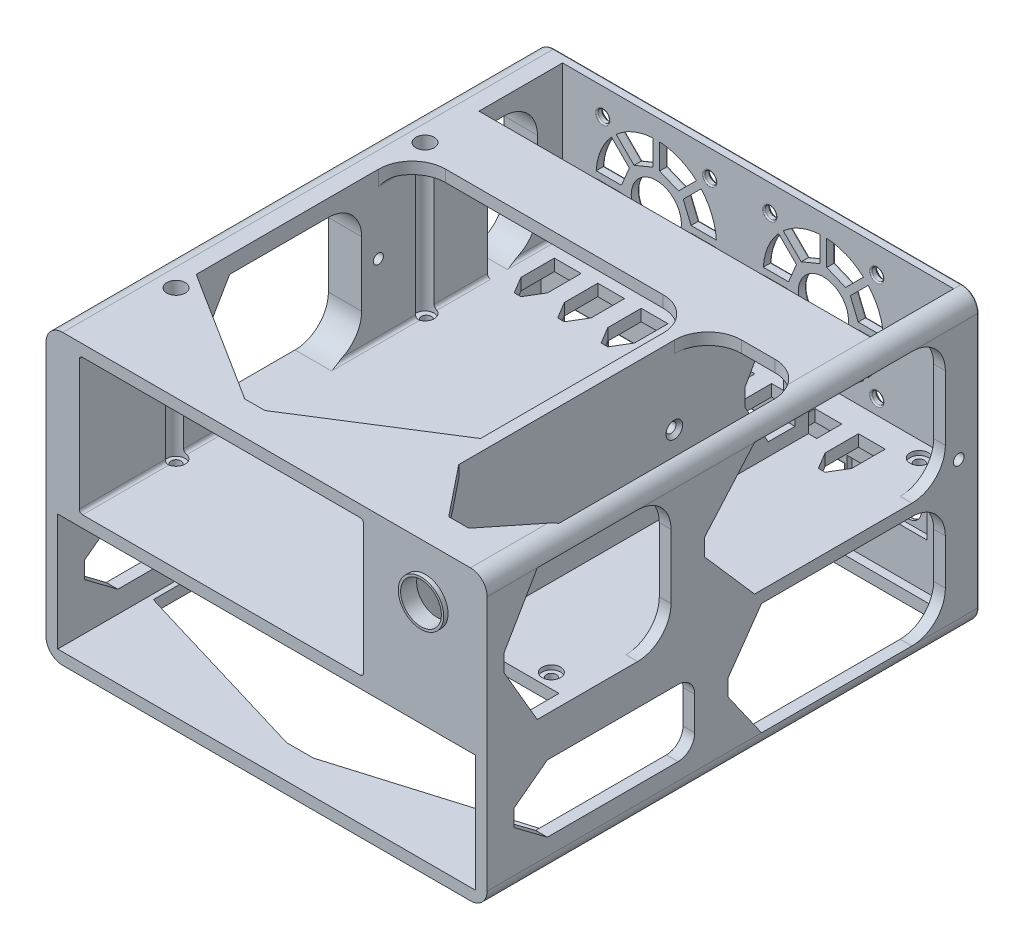
SolidWorks part; units mm, degrees
note: The reader was unsure of these and kept them because the rebuilt part matched: shared geometry of "草图12<5>", "草图14<3>", "草图12<6>", "草图12<7>".
ref_plane "Front Plane" through (0, 0, 0) normal (0, 0, 1) x (1, 0, 0)
ref_plane "Top Plane" through (0, 0, 0) normal (0, 1, 0) x (1, 0, 0)
ref_plane "Right Plane" through (0, 0, 0) normal (1, 0, 0) x (0, 0, -1)
other "Configuration Table"
sketch "草图1" plane through (0, 0, 0) normal (0, 0, 1) x (1, 0, 0)
  line L1 (-60.7557, 55.9139) -> (61.2443, 55.9139)
  line L2 (-65.7557, 50.9139) -> (-65.7557, -25.3861)
  line L3 (-60.7557, -30.3861) -> (61.2443, -30.3861)
  line L4 (66.2443, 50.9139) -> (66.2443, -25.3861)
  arc A0 (-65.7557, -25.3861) -> (-60.7557, -30.3861) centre (-60.7557, -25.3861) ccw
  arc A1 (61.2443, -30.3861) -> (66.2443, -25.3861) centre (61.2443, -25.3861) ccw
  arc A2 (66.2443, 50.9139) -> (61.2443, 55.9139) centre (61.2443, 50.9139) ccw
  arc A3 (-65.7557, 50.9139) -> (-60.7557, 55.9139) centre (-60.7557, 50.9139) cw
  point P8 (66.2443, -30.3861)
  point P11 (66.2443, 55.9139)
  point P14 (-65.7557, 55.9139)
  dimension "D3" = 5
  dimension "D1" = 132
  dimension "D2" = 86.3
extrude "凸台-拉伸1" add sketch "草图1" along normal blind 147.1
sketch "草图2" plane through (0, 0, 147.1) normal (0, 0, 1) x (1, 0, 0)
  line L0 (-65.7557, 50.9139) -> (-65.7557, -25.3861) construction
  line L1 (-54.8057, 52.4139) -> (28.2443, 52.4139)
  line L2 (-55.8057, 51.4139) -> (-55.8057, 12.6139)
  line L3 (-54.8057, 11.6139) -> (28.2443, 11.6139)
  line L4 (29.2443, 51.4139) -> (29.2443, 12.6139)
  line L5 (32.7443, 52.4139) -> (62.7443, 52.4139)
  line L6 (32.7443, 52.4139) -> (32.7443, 11.6139)
  line L7 (32.7443, 11.6139) -> (62.7443, 11.6139)
  line L8 (62.7443, 52.4139) -> (62.7443, 11.6139)
  line L9 (-62.2557, 8.1139) -> (62.7443, 8.1139)
  line L10 (-62.2557, 8.1139) -> (-62.2557, -26.8861)
  line L11 (-62.2557, -26.8861) -> (62.7443, -26.8861)
  line L12 (62.7443, 8.1139) -> (62.7443, -26.8861)
  line L13 (61.2443, 55.9139) -> (-60.7557, 55.9139) construction
  line L14 (-60.7557, -30.3861) -> (61.2443, -30.3861) construction
  line L15 (66.2443, -25.3861) -> (66.2443, 50.9139) construction
  arc A0 (-55.8057, 12.6139) -> (-54.8057, 11.6139) centre (-54.8057, 12.6139) ccw
  arc A1 (28.2443, 11.6139) -> (29.2443, 12.6139) centre (28.2443, 12.6139) ccw
  arc A2 (29.2443, 51.4139) -> (28.2443, 52.4139) centre (28.2443, 51.4139) ccw
  arc A3 (-55.8057, 51.4139) -> (-54.8057, 52.4139) centre (-54.8057, 51.4139) cw
  point P24 (29.2443, 11.6139)
  point P27 (29.2443, 52.4139)
  point P30 (-55.8057, 52.4139)
  dimension "D13" = 1
  dimension "D1" = 9.95
  dimension "D2" = 3.5
  dimension "D3" = 40.8
  dimension "D4" = 3.5
  dimension "D5" = 85.05
  dimension "D6" = 3.5
  dimension "D7" = 3.5
  dimension "D8" = 3.5
  dimension "D9" = 3.5
  dimension "D10" = 3.5
  dimension "D11" = 3.5
  dimension "D12" = 3.5
extrude "切除-拉伸1" cut sketch "草图2" against normal blind 144.6
sketch "草图4" plane through (0, 0, 0) normal (0, 0, -1) x (-1, 0, 0)
  line L0 (65.7557, 50.9139) -> (65.7557, -25.3861) construction
  line L1 (7.7557, 52.0139) -> (47.7557, 52.0139)
  line L2 (7.7557, 52.0139) -> (7.7557, 12.0139)
  line L3 (7.7557, 12.0139) -> (47.7557, 12.0139)
  line L4 (47.7557, 52.0139) -> (47.7557, 12.0139)
  line L5 (-42.2443, 52.0139) -> (-2.2443, 52.0139)
  line L6 (-42.2443, 52.0139) -> (-42.2443, 12.0139)
  line L7 (-42.2443, 12.0139) -> (-2.2443, 12.0139)
  line L8 (-2.2443, 52.0139) -> (-2.2443, 12.0139)
  line L9 (-61.2443, 55.9139) -> (60.7557, 55.9139) construction
  line L10 (-8.829, 44.0151) -> (-14.1764, 38.6676)
  line L11 (-11.8346, 33.0139) -> (-14.1764, 38.6676)
  line L12 (-15.5907, 40.0818) -> (-21.2443, 42.4236)
  line L13 (-23.2443, 42.4236) -> (-28.898, 40.0818)
  line L14 (-30.3122, 38.6676) -> (-32.654, 33.0139)
  line L15 (-32.654, 31.0139) -> (-30.3122, 25.3603)
  line L16 (-28.898, 23.946) -> (-23.2443, 21.6042)
  line L17 (-21.2443, 21.6042) -> (-15.5907, 23.946)
  line L18 (-14.1764, 25.3603) -> (-11.8346, 31.0139)
  line L20 (-23.2443, 49.9861) -> (-23.2443, 42.4236)
  line L22 (-21.2443, 49.9861) -> (-21.2443, 42.4236)
  line L23 (-10.2432, 45.4293) -> (-15.5907, 40.0818)
  line L24 (-4.2721, 31.0139) -> (-11.8346, 31.0139)
  line L25 (-4.2721, 33.0139) -> (-11.8346, 33.0139)
  line L26 (-10.2432, 18.5986) -> (-15.5907, 23.946)
  line L27 (-8.829, 20.0128) -> (-14.1764, 25.3603)
  line L28 (-23.2443, 14.0417) -> (-23.2443, 21.6042)
  line L29 (-21.2443, 14.0417) -> (-21.2443, 21.6042)
  line L30 (-35.6597, 20.0128) -> (-30.3122, 25.3603)
  line L31 (-34.2455, 18.5986) -> (-28.898, 23.946)
  line L32 (-40.2165, 33.0139) -> (-32.654, 33.0139)
  line L33 (-40.2165, 31.0139) -> (-32.654, 31.0139)
  line L34 (-34.2455, 45.4293) -> (-28.898, 40.0818)
  line L35 (-35.6597, 44.0151) -> (-30.3122, 38.6676)
  line L36 (28.7557, 49.9861) -> (28.7557, 42.4236)
  line L37 (28.7557, 42.4236) -> (34.4093, 40.0818)
  line L38 (2.7557, 52.0139) -> (2.7557, 12.0139) construction
  line L39 (39.7568, 45.4293) -> (34.4093, 40.0818)
  line L40 (41.171, 44.0151) -> (35.8236, 38.6676)
  line L41 (35.8236, 38.6676) -> (38.1654, 33.0139)
  line L42 (45.7279, 33.0139) -> (38.1654, 33.0139)
  line L43 (45.7279, 31.0139) -> (38.1654, 31.0139)
  line L44 (38.1654, 31.0139) -> (35.8236, 25.3603)
  line L45 (41.171, 20.0128) -> (35.8236, 25.3603)
  line L46 (39.7568, 18.5986) -> (34.4093, 23.946)
  line L47 (34.4093, 23.946) -> (28.7557, 21.6042)
  line L48 (28.7557, 14.0417) -> (28.7557, 21.6042)
  line L49 (26.7557, 14.0417) -> (26.7557, 21.6042)
  line L50 (26.7557, 21.6042) -> (21.102, 23.946)
  line L51 (15.7545, 18.5986) -> (21.102, 23.946)
  line L52 (14.3403, 20.0128) -> (19.6878, 25.3603)
  line L53 (19.6878, 25.3603) -> (17.346, 31.0139)
  line L54 (9.7835, 31.0139) -> (17.346, 31.0139)
  line L55 (9.7835, 33.0139) -> (17.346, 33.0139)
  line L56 (17.346, 33.0139) -> (19.6878, 38.6676)
  line L57 (14.3403, 44.0151) -> (19.6878, 38.6676)
  line L58 (15.7545, 45.4293) -> (21.102, 40.0818)
  line L59 (21.102, 40.0818) -> (26.7557, 42.4236)
  line L60 (26.7557, 49.9861) -> (26.7557, 42.4236)
  circle A0 centre (-38.2443, 48.0139) radius 1.75
  circle A1 centre (-6.2443, 48.0139) radius 1.75
  circle A2 centre (-38.2443, 16.0139) radius 1.75
  circle A3 centre (-6.2443, 16.0139) radius 1.75
  circle A4 centre (-22.2443, 32.0139) radius 7.5
  circle A5 centre (43.7557, 16.0139) radius 1.75
  arc A6 (-23.2443, 49.9861) -> (-34.2455, 45.4293) centre (-22.2443, 32.0139) ccw
  arc A7 (-10.2432, 45.4293) -> (-21.2443, 49.9861) centre (-22.2443, 32.0139) ccw
  arc A8 (-4.2721, 33.0139) -> (-8.829, 44.0151) centre (-22.2443, 32.0139) ccw
  arc A9 (-8.829, 20.0128) -> (-4.2721, 31.0139) centre (-22.2443, 32.0139) ccw
  circle A10 centre (11.7557, 16.0139) radius 1.75
  arc A11 (-21.2443, 14.0417) -> (-10.2432, 18.5986) centre (-22.2443, 32.0139) ccw
  arc A12 (-34.2455, 18.5986) -> (-23.2443, 14.0417) centre (-22.2443, 32.0139) ccw
  arc A13 (-40.2165, 31.0139) -> (-35.6597, 20.0128) centre (-22.2443, 32.0139) ccw
  arc A14 (-35.6597, 44.0151) -> (-40.2165, 33.0139) centre (-22.2443, 32.0139) ccw
  circle A15 centre (11.7557, 48.0139) radius 1.75
  circle A16 centre (43.7557, 48.0139) radius 1.75
  circle A17 centre (27.7557, 32.0139) radius 7.5
  arc A18 (41.171, 44.0151) -> (45.7279, 33.0139) centre (27.7557, 32.0139) cw
  arc A19 (28.7557, 49.9861) -> (39.7568, 45.4293) centre (27.7557, 32.0139) cw
  arc A20 (45.7279, 31.0139) -> (41.171, 20.0128) centre (27.7557, 32.0139) cw
  arc A21 (39.7568, 18.5986) -> (28.7557, 14.0417) centre (27.7557, 32.0139) cw
  arc A22 (26.7557, 14.0417) -> (15.7545, 18.5986) centre (27.7557, 32.0139) cw
  arc A23 (14.3403, 20.0128) -> (9.7835, 31.0139) centre (27.7557, 32.0139) cw
  arc A24 (9.7835, 33.0139) -> (14.3403, 44.0151) centre (27.7557, 32.0139) cw
  arc A25 (15.7545, 45.4293) -> (26.7557, 49.9861) centre (27.7557, 32.0139) cw
  point P68 (-22.2443, 32.0139)
  dimension "D9" = 3.5
  dimension "D10" = 20
  dimension "D11" = 20
  dimension "D13" = 36
  dimension "D14" = 15
  dimension "D15" = 16
  dimension "D16" = 16
  dimension "D17" = 16
  dimension "D18" = 16
  dimension "D19" = 16
  dimension "D20" = 16
  dimension "D21" = 16
  dimension "D22" = 16
  dimension "D1" = 40
  dimension "D2" = 10
  dimension "D3" = 40
  dimension "D4" = 18
  dimension "D5" = 40
  dimension "D6" = 40
  dimension "D7" = 3.9
  dimension "D8" = 3.9
  dimension "D23" = 2
  dimension "D24" = 1
  dimension "D25" = 8
extrude "切除-拉伸2" cut sketch "草图4" against normal blind 2.5 contours L20 A6 L34 L13 | L23 A7 L22 L12 | A1 | L25 A8 L10 L11 | L27 A9 L24 L18 | L29 A11 L26 L17 | L31 A12 L28 L16 | L33 A13 L30 L15 | L35 A14 L32 L14 | A4 | A22 L49 L50 L51 | A20 L43 L44 L45 | A18 L40 L41 L42 | A21 L46 L47 L48 | A23 L52 L53 L54 | A24 L55 L56 L57 | A25 L58 L59 L60 | A19 L36 L37 L39 | A17 | A16 | A5 | A0 | A3 | A2 | A10 | A15
sketch "草图5" plane through (0, 0, 0) normal (0, 0, -1) x (-1, 0, 0)
  line L0 (-61.2443, 55.9139) -> (60.7557, 55.9139) construction
  line L1 (-28.3443, -5.8861) -> (-11.1443, -5.8861)
  line L2 (-28.3443, -5.8861) -> (-28.3443, -20.3861)
  line L3 (-28.3443, -20.3861) -> (-11.1443, -20.3861)
  line L4 (-11.1443, -5.8861) -> (-11.1443, -20.3861)
  line L5 (-8.2443, -5.6861) -> (7.2557, -5.6861)
  line L6 (-8.2443, -5.6861) -> (-8.2443, -13.6861)
  line L7 (-8.2443, -13.6861) -> (7.2557, -13.6861)
  line L8 (7.2557, -5.6861) -> (7.2557, -13.6861)
  line L9 (9.9557, -6.2861) -> (26.2557, -6.2861)
  line L10 (9.9557, -6.2861) -> (9.9557, -22.8861)
  line L11 (9.9557, -22.8861) -> (26.2557, -22.8861)
  line L12 (26.2557, -6.2861) -> (26.2557, -22.8861)
  line L13 (28.3557, -6.3861) -> (44.3557, -6.3861)
  line L14 (28.3557, -6.3861) -> (28.3557, -12.8861)
  line L15 (28.3557, -12.8861) -> (44.3557, -12.8861)
  line L16 (44.3557, -6.3861) -> (44.3557, -12.8861)
  line L17 (47.4557, -6.4861) -> (57.4557, -6.4861)
  line L18 (47.4557, -6.4861) -> (47.4557, -19.4861)
  line L19 (47.4557, -19.4861) -> (57.4557, -19.4861)
  line L20 (57.4557, -6.4861) -> (57.4557, -19.4861)
  line L21 (65.7557, 50.9139) -> (65.7557, -25.3861) construction
  circle A0 centre (-46.2943, -8.1861) radius 3.75
  circle A1 centre (-35.1443, -8.1861) radius 3.75
  point P28 (28.3557, -9.6361)
  dimension "D21" = 7.5
  dimension "D22" = 6.8
  dimension "D23" = 2.3
  dimension "D24" = 11.15
  dimension "D25" = 2.3
  dimension "D1" = 62.4
  dimension "D2" = 8.3
  dimension "D3" = 13
  dimension "D4" = 10
  dimension "D5" = 62.3
  dimension "D6" = 3.1
  dimension "D7" = 16
  dimension "D8" = 6.5
  dimension "D9" = 62.2
  dimension "D10" = 61.6
  dimension "D11" = 61.8
  dimension "D12" = 2.1
  dimension "D13" = 16.3
  dimension "D14" = 16.6
  dimension "D15" = 2.7
  dimension "D16" = 15.5
  dimension "D17" = 8
  dimension "D18" = 2.9
  dimension "D19" = 17.2
  dimension "D20" = 14.5
extrude "切除-拉伸3" cut sketch "草图5" against normal blind 2.5
sketch "草图6" plane through (0, 0, 2.5) normal (0, 0, 1) x (1, 0, 0)
  line L1 (29.2943, -3.1861) -> (53.2943, -3.1861)
  line L2 (29.2943, -3.1861) -> (29.2943, -13.1861)
  line L3 (29.2943, -13.1861) -> (53.2943, -13.1861)
  line L4 (53.2943, -3.1861) -> (53.2943, -13.1861)
  circle A0 centre (46.2943, -8.1861) radius 3.75 construction
  dimension "D2" = 5
  dimension "D1" = 7
  dimension "D3" = 10
  dimension "D4" = 24
extrude "切除-拉伸4" cut sketch "草图6" against normal blind 1.5
sketch "草图7" plane through (0, 11.6139, 0) normal (0, 1, 0) x (1, 0, 0)
  line L0 (61.2443, 0) -> (-60.7557, 0) construction
  line L1 (66.2443, -147.1) -> (66.2443, 0) construction
  line L2 (-65.7557, -147.1) -> (-65.7557, 0) construction
  line L3 (-50.7557, -10) -> (-42.7557, -10)
  line L4 (-42.7557, -10) -> (-42.7557, -20)
  line L5 (-42.7557, -20) -> (-45.7557, -25)
  line L6 (-45.7557, -25) -> (-47.7557, -25)
  line L7 (-47.7557, -25) -> (-50.7557, -20)
  line L8 (-50.7557, -20) -> (-50.7557, -10)
  line L9 (-37.7557, -10) -> (-29.7557, -10)
  line L10 (-29.7557, -10) -> (-29.7557, -20)
  line L11 (-29.7557, -20) -> (-32.7557, -25)
  line L12 (-32.7557, -25) -> (-34.7557, -25)
  line L13 (-34.7557, -25) -> (-37.7557, -20)
  line L14 (-37.7557, -20) -> (-37.7557, -10)
  line L15 (-24.7557, -10) -> (-16.7557, -10)
  line L16 (-16.7557, -10) -> (-16.7557, -20)
  line L17 (-16.7557, -20) -> (-19.7557, -25)
  line L18 (-19.7557, -25) -> (-21.7557, -25)
  line L19 (-21.7557, -25) -> (-24.7557, -20)
  line L20 (-24.7557, -20) -> (-24.7557, -10)
  line L21 (-11.7557, -10) -> (-3.7557, -10)
  line L22 (-3.7557, -10) -> (-3.7557, -20)
  line L23 (-3.7557, -20) -> (-6.7557, -25)
  line L24 (-6.7557, -25) -> (-8.7557, -25)
  line L25 (-8.7557, -25) -> (-11.7557, -20)
  line L26 (-11.7557, -20) -> (-11.7557, -10)
  line L27 (1.2443, -10) -> (9.2443, -10)
  line L28 (9.2443, -10) -> (9.2443, -20)
  line L29 (9.2443, -20) -> (6.2443, -25)
  line L30 (6.2443, -25) -> (4.2443, -25)
  line L31 (4.2443, -25) -> (1.2443, -20)
  line L32 (1.2443, -20) -> (1.2443, -10)
  line L33 (14.2443, -10) -> (22.2443, -10)
  line L34 (22.2443, -10) -> (22.2443, -20)
  line L35 (22.2443, -20) -> (19.2443, -25)
  line L36 (19.2443, -25) -> (17.2443, -25)
  line L37 (17.2443, -25) -> (14.2443, -20)
  line L38 (14.2443, -20) -> (14.2443, -10)
  line L39 (27.2443, -10) -> (35.2443, -10)
  line L40 (35.2443, -10) -> (35.2443, -20)
  line L41 (35.2443, -20) -> (32.2443, -25)
  line L42 (32.2443, -25) -> (30.2443, -25)
  line L43 (30.2443, -25) -> (27.2443, -20)
  line L44 (27.2443, -20) -> (27.2443, -10)
  line L45 (40.2443, -10) -> (48.2443, -10)
  line L46 (48.2443, -10) -> (48.2443, -20)
  line L47 (48.2443, -20) -> (45.2443, -25)
  line L48 (45.2443, -25) -> (43.2443, -25)
  line L49 (43.2443, -25) -> (40.2443, -20)
  line L50 (40.2443, -20) -> (40.2443, -10)
  line L51 (61.2443, -147.1) -> (-60.7557, -147.1) construction
  line L52 (32.7443, -122.1) -> (62.7443, -122.1)
  line L53 (32.7443, -122.1) -> (32.7443, -147.1)
  line L54 (32.7443, -147.1) -> (62.7443, -147.1)
  line L55 (62.7443, -122.1) -> (62.7443, -147.1)
  circle A0 centre (-55.3557, -43.7) radius 1.5
  circle A1 centre (55.6443, -7.2) radius 1.5
  circle A2 centre (56.1443, -117.8) radius 1.5
  circle A3 centre (-55.3557, -118.6) radius 1.5
  dimension "D1" = 3
  dimension "D2" = 7.2
  dimension "D3" = 10.6
  dimension "D4" = 10.1
  dimension "D5" = 110.6
  dimension "D6" = 43.7
  dimension "D7" = 10.4
  dimension "D8" = 74.9
  dimension "D9" = 10.4
  dimension "D10" = 10
  dimension "D11" = 15
  dimension "D12" = 8
  dimension "D13" = 2
  dimension "D14" = 3
  dimension "D15" = 5
  dimension "D16" = 5
  dimension "D17" = 15
  dimension "D19" = 5
  dimension "D20" = 3.5
  dimension "D21" = 30
  dimension "D22" = 25
  dimension "D18" = 8
extrude "切除-拉伸5" cut sketch "草图7" against normal blind 3.5
sketch "草图8" plane through (0, 11.6139, 0) normal (0, 1, 0) x (1, 0, 0)
  line L0 (-65.7557, -147.1) -> (-65.7557, 0) construction
  line L1 (61.2443, 0) -> (-60.7557, 0) construction
  circle A0 centre (-55.7557, -43.7) radius 2.75
  circle A1 centre (-55.3557, -118.6) radius 2.75
  circle A2 centre (56.1443, -117.8) radius 2.75
  circle A3 centre (55.6443, -7.2) radius 2.75
  dimension "D1" = 5.5
  dimension "D2" = 10
  dimension "D3" = 43.7
extrude "切除-拉伸6" cut sketch "草图8" against normal blind 1.3 and the other way blind 50
sketch "草图9" plane through (0, 55.9139, 0) normal (0, 1, 0) x (1, 0, 0)
  line L0 (-55.8057, -112.1) -> (-55.8057, -57.5)
  line L1 (-55.8057, -2.5) -> (61.2443, -2.5)
  line L2 (-55.8057, -2.5) -> (-55.8057, -27.5)
  line L3 (-55.8057, -27.5) -> (61.2443, -27.5)
  line L4 (61.2443, -2.5) -> (61.2443, -27.5)
  line L5 (-45.8057, -47.5) -> (19.2443, -47.5)
  line L6 (29.2443, -57.5) -> (29.2443, -112.1)
  line L7 (29.2443, -112.1) -> (-10.2807, -137.1)
  line L8 (-10.2807, -137.1) -> (-16.2807, -137.1)
  line L9 (-16.2807, -137.1) -> (-55.8057, -112.1)
  line L10 (32.7443, -122.1) -> (32.7443, -57.5)
  line L11 (42.7443, -47.5) -> (52.7443, -47.5)
  line L12 (62.7443, -57.5) -> (62.7443, -122.1)
  line L13 (62.7443, -122.1) -> (50.7443, -137.1)
  line L14 (50.7443, -137.1) -> (44.7443, -137.1)
  line L15 (44.7443, -137.1) -> (32.7443, -122.1)
  line L16 (61.2443, 0) -> (-60.7557, 0) construction
  line L17 (66.2443, -147.1) -> (66.2443, 0) construction
  line L18 (-65.7557, -147.1) -> (-65.7557, 0) construction
  line L19 (61.2443, -147.1) -> (-60.7557, -147.1) construction
  arc A0 (-55.8057, -57.5) -> (-45.8057, -47.5) centre (-45.8057, -57.5) cw
  arc A1 (29.2443, -57.5) -> (19.2443, -47.5) centre (19.2443, -57.5) ccw
  arc A2 (62.7443, -57.5) -> (52.7443, -47.5) centre (52.7443, -57.5) ccw
  arc A3 (32.7443, -57.5) -> (42.7443, -47.5) centre (42.7443, -57.5) cw
  point P26 (-55.8057, -47.5)
  point P29 (29.2443, -47.5)
  dimension "D21" = 10
  dimension "D1" = 2.5
  dimension "D2" = 5
  dimension "D3" = 9.95
  dimension "D4" = 25
  dimension "D5" = 20
  dimension "D6" = 10
  dimension "D7" = 9.95
  dimension "D8" = 85.05
  dimension "D9" = 6
  dimension "D10" = 39.525
  dimension "D11" = 25
  dimension "D12" = 25
  dimension "D13" = 20
  dimension "D14" = 10
  dimension "D15" = 3.5
  dimension "D16" = 3.5
  dimension "D17" = 6
  dimension "D18" = 12
  dimension "D19" = 15
  dimension "D20" = 15
extrude "切除-拉伸7" cut sketch "草图9" against normal blind 6
sketch "草图10" plane through (0, 11.6139, 0) normal (0, 1, 0) x (1, 0, 0)
  line L0 (61.2443, -2.5) -> (-55.8057, -2.5) construction
  line L1 (27.2443, -2.5) -> (33.7443, -2.5)
  line L2 (27.2443, -2.5) -> (27.2443, -17.5)
  line L3 (27.2443, -17.5) -> (33.7443, -17.5)
  line L4 (33.7443, -2.5) -> (33.7443, -17.5)
  line L6 (32.7443, -2.5) -> (32.7443, -10) construction
  line L7 (29.2443, -2.5) -> (29.2443, -27.5) construction
  dimension "D1" = 1
  dimension "D2" = 2
  dimension "D3" = 15
extrude "切除-拉伸8" cut sketch "草图10" along normal blind 48
sketch "草图11" plane through (66.2443, 0, 0) normal (1, 0, 0) x (0, 0, -1)
  line L0 (-132.1, 50.9139) -> (-102.1, 50.9139)
  line L1 (-92.1, 40.9139) -> (-92.1, 21.6139)
  line L2 (-102.1, 11.6139) -> (-132.1, 11.6139)
  line L3 (-132.1, 11.6139) -> (-142.1, 28.7639)
  line L4 (-142.1, 28.7639) -> (-142.1, 33.7639)
  line L5 (-142.1, 33.7639) -> (-132.1, 50.9139)
  line L6 (-67.1, 50.9139) -> (-20, 50.9139)
  line L7 (-10, 40.9139) -> (-10, 21.6139)
  line L8 (-20, 11.6139) -> (-67.1, 11.6139)
  line L9 (-67.1, 11.6139) -> (-82.1, 28.7639)
  line L10 (-82.1, 28.7639) -> (-82.1, 33.7639)
  line L11 (-82.1, 33.7639) -> (-67.1, 50.9139)
  line L12 (-65, 8.1139) -> (-20, 8.1139)
  line L13 (-10, -1.8861) -> (-10, -15.3861)
  line L14 (-20, -25.3861) -> (-65, -25.3861)
  line L15 (-65, -25.3861) -> (-75, -11.1361)
  line L16 (-75, -11.1361) -> (-75, -6.1361)
  line L17 (-75, -6.1361) -> (-65, 8.1139)
  line L18 (0, -25.3861) -> (0, 50.9139) construction
  line L19 (-147.1, -25.3861) -> (-147.1, 50.9139) construction
  line L20 (-147.1, 55.9139) -> (-123.975, 55.9139) construction
  line L21 (-129.1, -0.3861) -> (-90, -0.3861)
  line L22 (-147.1, -30.3861) -> (0, -30.3861) construction
  line L23 (-85, -5.3861) -> (-85, -15.3861)
  line L24 (-90, -20.3861) -> (-129.1, -20.3861)
  line L25 (-129.1, -20.3861) -> (-139.1, -12.8861)
  line L26 (-139.1, -12.8861) -> (-139.1, -7.8861)
  line L27 (-139.1, -7.8861) -> (-129.1, -0.3861)
  arc A0 (-102.1, 11.6139) -> (-92.1, 21.6139) centre (-102.1, 21.6139) ccw
  arc A1 (-92.1, 40.9139) -> (-102.1, 50.9139) centre (-102.1, 40.9139) ccw
  arc A2 (-10, 40.9139) -> (-20, 50.9139) centre (-20, 40.9139) ccw
  arc A3 (-20, 11.6139) -> (-10, 21.6139) centre (-20, 21.6139) ccw
  arc A4 (-20, -25.3861) -> (-10, -15.3861) centre (-20, -15.3861) ccw
  arc A5 (-10, -1.8861) -> (-20, 8.1139) centre (-20, -1.8861) ccw
  arc A6 (-90, -20.3861) -> (-85, -15.3861) centre (-90, -15.3861) ccw
  arc A7 (-85, -5.3861) -> (-90, -0.3861) centre (-90, -5.3861) ccw
  point P29 (-92.1, 11.6139)
  point P32 (-92.1, 50.9139)
  point P35 (-10, 50.9139)
  point P38 (-10, 11.6139)
  point P41 (-10, -25.3861)
  point P44 (-10, 8.1139)
  point P53 (-85, -20.3861)
  point P56 (-85, -0.3861)
  dimension "D24" = 10
  dimension "D33" = 5
  dimension "D1" = 10
  dimension "D2" = 10
  dimension "D3" = 65
  dimension "D4" = 5
  dimension "D5" = 5
  dimension "D6" = 39.3
  dimension "D7" = 5
  dimension "D8" = 17.15
  dimension "D9" = 10
  dimension "D10" = 10
  dimension "D11" = 50
  dimension "D12" = 10
  dimension "D13" = 5
  dimension "D14" = 39.3
  dimension "D15" = 17.15
  dimension "D16" = 15
  dimension "D17" = 15
  dimension "D18" = 5
  dimension "D19" = 33.5
  dimension "D20" = 5
  dimension "D21" = 14.25
  dimension "D22" = 10
  dimension "D23" = 10
  dimension "D25" = 10
  dimension "D26" = 5
  dimension "D27" = 8
  dimension "D28" = 10
  dimension "D29" = 20
  dimension "D30" = 7.5
  dimension "D31" = 10
  dimension "D32" = 10
extrude "切除-拉伸9" cut sketch "草图11" against normal blind 3.5
sketch "草图12" plane through (-65.7557, 0, 0) normal (-1, 0, 0) x (0, 0, 1)
  line L0 (42.6, 50.9139) -> (20, 50.9139)
  line L1 (10, 40.9139) -> (10, 21.6139)
  line L2 (20, 11.6139) -> (42.6, 11.6139)
  line L3 (42.6, 11.6139) -> (52.6, 28.7639)
  line L4 (52.6, 28.7639) -> (52.6, 33.7639)
  line L5 (52.6, 33.7639) -> (42.6, 50.9139)
  line L6 (102.1, 50.9139) -> (72.6, 50.9139)
  line L7 (62.6, 40.9139) -> (62.6, 21.6139)
  line L8 (72.6, 11.6139) -> (102.1, 11.6139)
  line L9 (102.1, 11.6139) -> (112.1, 28.7639)
  line L10 (112.1, 28.7639) -> (112.1, 33.7639)
  line L11 (112.1, 33.7639) -> (102.1, 50.9139)
  line L12 (65, -25.3861) -> (20, -25.3861)
  line L13 (10, -15.3861) -> (10, -1.8861)
  line L14 (20, 8.1139) -> (65, 8.1139)
  line L15 (65, 8.1139) -> (75, -6.1361)
  line L16 (75, -6.1361) -> (75, -11.1361)
  line L17 (75, -11.1361) -> (65, -25.3861)
  line L18 (147.1, 50.9139) -> (147.1, -25.3861) construction
  line L19 (0, 50.9139) -> (0, -25.3861) construction
  line L20 (147.1, -30.3861) -> (0, -30.3861) construction
  line L21 (147.1, 55.9139) -> (0, 55.9139) construction
  line L22 (129.1, -20.3861) -> (90, -20.3861)
  line L23 (85, -15.3861) -> (85, -5.3861)
  line L24 (90, -0.3861) -> (129.1, -0.3861)
  line L25 (129.1, -0.3861) -> (139.1, -7.8861)
  line L26 (139.1, -7.8861) -> (139.1, -12.8861)
  line L27 (139.1, -12.8861) -> (129.1, -20.3861)
  circle A0 centre (117.1, 32.7139) radius 1.5
  circle A1 centre (57.6, 32.7139) radius 1.5
  arc A2 (20, -25.3861) -> (10, -15.3861) centre (20, -15.3861) cw
  arc A3 (10, -1.8861) -> (20, 8.1139) centre (20, -1.8861) cw
  arc A4 (72.6, 11.6139) -> (62.6, 21.6139) centre (72.6, 21.6139) cw
  arc A5 (72.6, 50.9139) -> (62.6, 40.9139) centre (72.6, 40.9139) ccw
  arc A6 (20, 11.6139) -> (10, 21.6139) centre (20, 21.6139) cw
  arc A7 (10, 40.9139) -> (20, 50.9139) centre (20, 40.9139) cw
  arc A8 (90, -20.3861) -> (85, -15.3861) centre (90, -15.3861) cw
  arc A9 (85, -5.3861) -> (90, -0.3861) centre (90, -5.3861) cw
  point P33 (10, -25.3861)
  point P36 (10, 8.1139)
  point P39 (62.6, 11.6139)
  point P42 (62.6, 50.9139)
  point P45 (10, 11.6139)
  point P48 (10, 50.9139)
  point P57 (85, -20.3861)
  point P60 (85, -0.3861)
  line M6 (0, -25.3861) -> (147.1, -25.3861)
  line M8 (147.1, 50.9139) -> (0, 50.9139)
  dimension "D24" = 3
  dimension "D25" = 30
  dimension "D26" = 23.2
  dimension "D27" = 59.5
  dimension "D28" = 23.2
  dimension "D29" = 10
  dimension "D39" = 5
  dimension "D2" = 35
  dimension "D3" = 10
  dimension "D4" = 10
  dimension "D5" = 33.5
  dimension "D6" = 14.25
  dimension "D7" = 5
  dimension "D8" = 5
  dimension "D9" = 10
  dimension "D10" = 10
  dimension "D11" = 39.3
  dimension "D12" = 17.15
  dimension "D13" = 17.15
  dimension "D14" = 49.5
  dimension "D15" = 5
  dimension "D16" = 10
  dimension "D17" = 10
  dimension "D18" = 10
  dimension "D19" = 39.3
  dimension "D20" = 5
  dimension "D21" = 17.15
  dimension "D22" = 10
  dimension "D23" = 10
  dimension "D30" = 65
  dimension "D31" = 10
  dimension "D32" = 8
  dimension "D33" = 10
  dimension "D34" = 20
  dimension "D35" = 5
  dimension "D36" = 7.5
  dimension "D37" = 10
  dimension "D38" = 10
extrude "切除-拉伸13" cut sketch "草图12" against normal blind 12 contours L10 L11 L7 L8 L9 M8 | A0 | L17 L16 L15 L14 L13 M6 | A1
extrude "切除-拉伸14" cut sketch "草图12<5>" against normal blind 6 contours L4 L5 L1 L2 L3 M8
sketch "草图12<5>" plane through (-65.7557, 0, 0) normal (-1, 0, 0) x (0, 0, 1) same geometry as "草图12"
sketch "草图14" plane through (-65.7557, 0, 0) normal (-1, 0, 0) x (0, 0, 1)
  line L0 (10, 40.9139) -> (10, 21.6139) construction
  line L1 (20, 50.9139) -> (25, 50.9139)
  line L2 (10, 40.9139) -> (10, 21.6139)
  line L3 (20, 11.6139) -> (25, 11.6139)
  line L4 (25, 50.9139) -> (25, 11.6139)
  line L5 (42.6, 50.9139) -> (20, 50.9139) construction
  line L6 (20, 11.6139) -> (42.6, 11.6139) construction
  circle A0 centre (57.6, 32.7139) radius 3
  circle A1 centre (117.1, 32.7139) radius 3
  arc A2 (20, 11.6139) -> (10, 21.6139) centre (20, 21.6139) cw
  arc A3 (10, 40.9139) -> (20, 50.9139) centre (20, 40.9139) cw
  point P20 (10, 50.9139)
  circle M4 centre (57.6, 32.7139) radius 1.5
  circle M5 centre (117.1, 32.7139) radius 1.5
  arc M6 (10, 40.9139) -> (20, 50.9139) centre (20, 40.9139) cw
  line M31 (42.6, 11.6139) -> (20, 11.6139)
  arc M32 (20, 11.6139) -> (10, 21.6139) centre (20, 21.6139) cw
  line M33 (10, 21.6139) -> (10, 40.9139)
  dimension "D2" = 6
  dimension "D3" = 6
  dimension "D4" = 10
  dimension "D1" = 15
extrude "切除-拉伸15" cut sketch "草图14" against normal blind 6.45 contours A0 M4 | A1 M5
extrude "切除-拉伸16" cut sketch "草图14<3>" against normal blind 12 contours L4 L1 M6 M33 M32 M31
sketch "草图14<3>" plane through (-65.7557, 0, 0) normal (-1, 0, 0) x (0, 0, 1) same geometry as "草图14"
extrude "切除-拉伸17" cut sketch "草图12<6>" against normal blind 100 contours A1 | A0
sketch "草图12<6>" plane through (-65.7557, 0, 0) normal (-1, 0, 0) x (0, 0, 1) same geometry as "草图12"
sketch "草图15" plane through (0, -30.3861, 0) normal (0, -1, 0) x (1, 0, 0)
  line L0 (-60.7557, 5) -> (61.2443, 5)
  line L1 (61.2443, 5) -> (61.2443, 120)
  line L2 (61.2443, 120) -> (4.2443, 137.1)
  line L3 (4.2443, 137.1) -> (-3.7557, 137.1)
  line L4 (-3.7557, 137.1) -> (-60.7557, 120)
  line L5 (-60.7557, 120) -> (-60.7557, 5)
  line L6 (-60.7557, 0) -> (61.2443, 0) construction
  line L7 (66.2443, 65) -> (66.2443, 20) construction
  line L8 (-65.7557, 20) -> (-65.7557, 65) construction
  line L9 (-60.7557, 147.1) -> (61.2443, 147.1) construction
  dimension "D1" = 8
  dimension "D2" = 5
  dimension "D3" = 5
  dimension "D4" = 5
  dimension "D5" = 57
  dimension "D6" = 115
  dimension "D7" = 115
  dimension "D8" = 10
extrude "切除-拉伸18" cut sketch "草图15" against normal blind 3.5
sketch "草图16" plane through (66.2443, 0, 0) normal (1, 0, 0) x (0, 0, -1)
  line L0 (-27.5, 55.9139) -> (-2.5, 55.9139) construction
  line L1 (0, -25.3861) -> (0, 50.9139) construction
  circle A0 centre (-6, 15.9139) radius 1.6
  dimension "D1" = 3.2
  dimension "D2" = 40
  dimension "D3" = 6
extrude "切除-拉伸19" cut sketch "草图16" against normal through all
sketch "草图19" plane through (32.7443, 0, 0) normal (1, 0, 0) x (0, 0, -1)
  line L0 (-20, 50.9139) -> (-67.1, 50.9139) construction
  line L5 (-29.5, 45.5139) -> (-21.5, 45.5139)
  line L6 (-21.5, 45.5139) -> (-21.5, 15.5139)
  line L7 (-21.5, 15.5139) -> (-29.5, 15.5139)
  line L8 (-29.5, 15.5139) -> (-36.5, 28.0139)
  line L9 (-36.5, 28.0139) -> (-36.5, 33.0139)
  line L10 (-36.5, 33.0139) -> (-29.5, 45.5139)
  line L14 (-17.5, 49.9139) -> (-17.5, 11.6139) construction
  dimension "D1" = 4
  dimension "D2" = 15
  dimension "D3" = 5
  dimension "D4" = 30
  dimension "D5" = 12.5
  dimension "D6" = 7
  dimension "D7" = 7
  dimension "D8" = 5.4
extrude "切除-拉伸21" cut sketch "草图19" against normal blind 3.5
sketch "草图20" plane through (32.7443, 0, 0) normal (1, 0, 0) x (0, 0, -1)
  line L0 (-122.1, 8.1139) -> (-147.1, 8.1139) construction
  line L1 (-147.1, 52.4139) -> (-143.6, 52.4139)
  line L2 (-147.1, 52.4139) -> (-147.1, 8.1139)
  line L3 (-147.1, 8.1139) -> (-143.6, 8.1139)
  line L4 (-143.6, 52.4139) -> (-143.6, 8.1139)
  line L6 (-147.1, -25.3861) -> (-147.1, 50.9139) construction
  line L8 (-147.1, 55.9139) -> (-123.975, 55.9139) construction
  dimension "D1" = 3.5
  dimension "D2" = 3.5
extrude "凸台-拉伸2" add sketch "草图20" along normal blind 30
sketch "草图21" plane through (0, 0, 147.1) normal (0, 0, 1) x (1, 0, 0)
  line L0 (61.2443, 55.9139) -> (-60.7557, 55.9139) construction
  line L1 (66.2443, -25.3861) -> (66.2443, 50.9139) construction
  circle A0 centre (47.7443, 40.6639) radius 6.8
  dimension "D1" = 15.25
  dimension "D2" = 13.6
  dimension "D3" = 18.5
extrude "凸台-拉伸3" add sketch "草图21" along normal blind 1.3
sketch "草图22" plane through (0, 0, 148.4) normal (0, 0, 1) x (1, 0, 0)
  circle A0 centre (47.7443, 40.6639) radius 6.1
  dimension "D1" = 12.2
extrude "切除-拉伸22" cut sketch "草图22" against normal blind 5
chamfer "倒角1" distance 1 angle 45 10 edges at (32.7443, 31.2139, 117.1) (32.7443, 31.2139, 57.6) (-45.5057, 16.0139, 0) (-10.0057, 16.0139, 0) (-10.0057, 48.0139, 0) (-45.5057, 48.0139, 0) (4.4943, 16.0139, 0) (4.4943, 48.0139, 0) (36.4943, 48.0139, 0) (36.4943, 16.0139, 0)
fillet "圆角1" radius 0.4 104 edges at (-26.7557, 17.823, 0) (-23.9288, 22.7751, 0) (-18.4283, 21.2723, 0) (-20.8674, 15.3841, 0) (-38.4973, 41.3413, 0) (-36.9945, 35.8408, 0) (-41.9466, 33.0139, 0) (-44.3855, 38.9022, 0) (-17.014, 22.6865, 0) (-18.5169, 28.1871, 0) (-13.5647, 31.0139, 0) (-11.1258, 25.1256, 0) (-13.5647, 33.0139, 0) (-18.5169, 35.8408, 0) (-17.014, 41.3413, 0) (-11.1258, 38.9022, 0) (5.6145, 38.9022, 0) (11.5027, 41.3413, 0) (13.0055, 35.8408, 0) (8.0534, 33.0139, 0) (38.8742, 38.9022, 0) (36.4353, 33.0139, 0) (31.4831, 35.8408, 0) (32.986, 41.3413, 0) (29.1326, 15.3841, 0) (23.2443, 17.823, 0) (26.0712, 22.7751, 0) (31.5717, 21.2723, 0) (-35.2557, 32.0139, 0) (-28.7557, 46.2049, 0) (-31.5825, 41.2527, 0) (-37.0831, 42.7556, 0) (-34.644, 48.6438, 0) (0.2443, -30.3861, 0) (64.7799, -28.9216, 0) (66.2443, 12.7639, 0) (64.7799, 54.4495, 0) (0.2443, 55.9139, 0) (-64.2912, 54.4495, 0) (-65.7557, 12.7639, 0) (-64.2912, -28.9216, 0) (29.1326, 48.6438, 0) (31.5717, 42.7556, 0) (26.0712, 41.2527, 0) (23.2443, 46.2049, 0) (15.356, 15.3841, 0) (12.9169, 21.2723, 0) (18.4175, 22.7751, 0) (21.2443, 17.823, 0) (38.8742, 25.1256, 0) (32.986, 22.6865, 0) (31.4831, 28.1871, 0) (36.4353, 31.0139, 0) (15.356, 48.6438, 0) (21.2443, 46.2049, 0) (18.4175, 41.2527, 0) (12.9169, 42.7556, 0) (5.6145, 25.1256, 0) (8.0534, 31.0139, 0) (13.0055, 28.1871, 0) (11.5027, 22.6865, 0) (-18.4283, 42.7556, 0) (-23.9288, 41.2527, 0) (-26.7557, 46.2049, 0) (-20.8674, 48.6438, 0) (-37.0831, 21.2723, 0) (-31.5825, 22.7751, 0) (-28.7557, 17.823, 0) (-34.644, 15.3841, 0) (-41.9466, 31.0139, 0) (-36.9945, 28.1871, 0) (-38.4973, 22.6865, 0) (-44.3855, 25.1256, 0) (14.7443, 32.0139, 0) (11.1443, -13.1361, 0) (19.7443, -5.8861, 0) (28.3443, -13.1361, 0) (19.7443, -20.3861, 0) (-7.2557, -9.6861, 0) (0.4943, -5.6861, 0) (8.2443, -9.6861, 0) (0.4943, -13.6861, 0) (-26.2557, -14.5861, 0) (-18.1057, -6.2861, 0) (-9.9557, -14.5861, 0) (-18.1057, -22.8861, 0) (-44.3557, -9.6361, 0) (-36.3557, -6.3861, 0) (-28.3557, -9.6361, 0) (-36.3557, -12.8861, 0) (-57.4557, -12.9861, 0) (-52.4557, -6.4861, 0) (-47.4557, -12.9861, 0) (-52.4557, -19.4861, 0) (42.5443, -8.1861, 0) (31.3943, -8.1861, 0) (40.9943, 16.0139, 0) (40.9943, 48.0139, 0) (8.9943, 48.0139, 0) (8.9943, 16.0139, 0) (-41.0057, 48.0139, 0) (-9.0057, 48.0139, 0) (-9.0057, 16.0139, 0) (-41.0057, 16.0139, 0)
fillet "圆角2" radius 0.4 28 edges at (-45.5057, 16.0139, 2.5) (-45.5057, 48.0139, 2.5) (-10.0057, 16.0139, 2.5) (4.4943, 16.0139, 2.5) (-10.0057, 48.0139, 2.5) (4.4943, 48.0139, 2.5) (36.4943, 48.0139, 2.5) (36.4943, 16.0139, 2.5) (-52.4557, -19.4861, 2.5) (-57.4557, -12.9861, 2.5) (-52.4557, -6.4861, 2.5) (-47.4557, -12.9861, 2.5) (-36.3557, -12.8861, 2.5) (-44.3557, -9.6361, 2.5) (-36.3557, -6.3861, 2.5) (-28.3557, -9.6361, 2.5) (-18.1057, -22.8861, 2.5) (-26.2557, -14.5861, 2.5) (-18.1057, -6.2861, 2.5) (-9.9557, -14.5861, 2.5) (0.4943, -13.6861, 2.5) (-7.2557, -9.6861, 2.5) (0.4943, -5.6861, 2.5) (8.2443, -9.6861, 2.5) (19.7443, -20.3861, 2.5) (11.1443, -13.1361, 2.5) (19.7443, -5.8861, 2.5) (28.3443, -13.1361, 2.5)
chamfer "倒角4" distance 1 angle 45 2 edges at (-65.7557, 29.7139, 117.1) (-65.7557, 29.7139, 57.6)
sketch "草图23" plane through (27.2443, 0, 0) normal (1, 0, 0) x (0, 0, -1)
  line L0 (-67.1, 11.6139) -> (-20, 11.6139) construction
  line L1 (-25.5, 11.6139) -> (-17.5, 11.6139)
  line L2 (-25.5, 11.6139) -> (-25.5, 8.1139)
  line L3 (-25.5, 8.1139) -> (-17.5, 8.1139)
  line L4 (-17.5, 11.6139) -> (-17.5, 8.1139)
  line L5 (-17.5, 49.9139) -> (-17.5, 11.6139) construction
  line L6 (-20, 8.1139) -> (-65, 8.1139) construction
  dimension "D1" = 8
extrude "凸台-拉伸4" add sketch "草图23" along normal blind 8
fillet "圆角3" radius 10 1 edges at (30.9943, 49.9139, 17.5)
fillet "圆角4" radius 2 1 edges at (30.9943, 49.9139, 27.5)
extrude "切除-拉伸23" cut sketch "草图12<7>" against normal blind 5 contours A9 L23 A8 L22 L27 L26 L25 L24
sketch "草图12<7>" plane through (-65.7557, 0, 0) normal (-1, 0, 0) x (0, 0, 1) same geometry as "草图12"
sketch "草图25" plane through (-59.7557, 0, 0) normal (-1, 0, 0) x (0, 0, 1)
  line L0 (25, 49.3139) -> (41, 49.3139)
  line L1 (25, 39.6139) -> (33, 39.6139)
  line L2 (25, 39.6139) -> (25, 37.6139)
  line L3 (25, 37.6139) -> (47, 37.6139)
  line L4 (47, 38.6139) -> (47, 37.6139)
  line L5 (25, 24.9139) -> (47, 24.9139)
  line L6 (25, 24.9139) -> (25, 22.9139)
  line L7 (25, 22.9139) -> (33, 22.9139)
  line L8 (47, 24.9139) -> (47, 23.9139)
  line L9 (25, 15.2139) -> (33, 15.2139)
  line L10 (25, 15.2139) -> (25, 11.6139)
  line L11 (25, 11.6139) -> (45, 11.6139)
  line L12 (45, 16.2139) -> (45, 11.6139)
  line L14 (25, 49.3139) -> (25, 47.3139)
  line L15 (25, 47.3139) -> (33, 47.3139)
  line L16 (43, 47.3139) -> (43, 46.3139)
  line L17 (20, 11.6139) -> (42.6, 11.6139) construction
  line L19 (25, 50.9139) -> (25, 11.6139) construction
  line L20 (42.6, 50.9139) -> (25, 50.9139) construction
  line L21 (33, 39.6139) -> (33, 40.6139)
  line L22 (33, 40.6139) -> (45, 40.6139)
  line L23 (33, 47.3139) -> (33, 46.3139)
  line L24 (33, 46.3139) -> (43, 46.3139)
  line L26 (33, 15.2139) -> (33, 16.2139)
  line L27 (33, 16.2139) -> (45, 16.2139)
  line L29 (33, 22.9139) -> (33, 21.9139)
  line L30 (33, 21.9139) -> (45, 21.9139)
  arc A0 (41, 49.3139) -> (43, 47.3139) centre (41, 47.3139) cw
  arc A1 (45, 21.9139) -> (47, 23.9139) centre (45, 23.9139) ccw
  arc A2 (47, 38.6139) -> (45, 40.6139) centre (45, 38.6139) ccw
  point P15 (43, 49.3139)
  dimension "D20" = 2
  dimension "D21" = 2
  dimension "D1" = 12.7
  dimension "D2" = 2
  dimension "D3" = 3.85
  dimension "D4" = 22
  dimension "D5" = 2
  dimension "D6" = 2
  dimension "D7" = 3.6
  dimension "D8" = 18
  dimension "D9" = 20
  dimension "D10" = 22
  dimension "D11" = 1
  dimension "D12" = 1
  dimension "D13" = 1
  dimension "D14" = 1
  dimension "D15" = 1.6
  dimension "D16" = 8
  dimension "D17" = 8
  dimension "D18" = 8
  dimension "D19" = 8
extrude "凸台-拉伸5" add sketch "草图25" along normal blind 6
fillet "圆角5" radius 1 3 edges at (-62.7557, 24.9139, 47) (-62.7557, 37.6139, 47) (-62.7557, 46.3139, 43)
sketch "草图26" plane through (-65.7557, 0, 0) normal (-1, 0, 0) x (0, 0, 1)
  line L0 (25, 32.6139) -> (46, 32.6139)
  line L1 (25, 37.6139) -> (46, 37.6139)
  line L2 (25, 37.6139) -> (25, 32.6139)
  line L3 (25, 24.9139) -> (46, 24.9139)
  line L4 (46, 37.6139) -> (46, 32.6139)
  line L5 (25, 29.9139) -> (46, 29.9139)
  line L6 (25, 29.9139) -> (25, 24.9139)
  line L7 (46, 29.9139) -> (46, 24.9139)
  arc A0 (47, 23.9139) -> (46, 24.9139) centre (46, 23.9139) ccw construction
  arc A1 (47, 23.9139) -> (46, 24.9139) centre (46, 23.9139) ccw construction
  dimension "D1" = 21
  dimension "D2" = 2.7
  dimension "D3" = 5
extrude "凸台-拉伸6" add sketch "草图26" against normal blind 1.5
fillet "圆角6" radius 3 2 edges at (-65.0057, 29.9139, 25) (-65.0057, 32.6139, 25)
fillet "圆角7" radius 0.5 2 edges at (-65.0057, 29.9139, 46) (-65.0057, 32.6139, 46)
